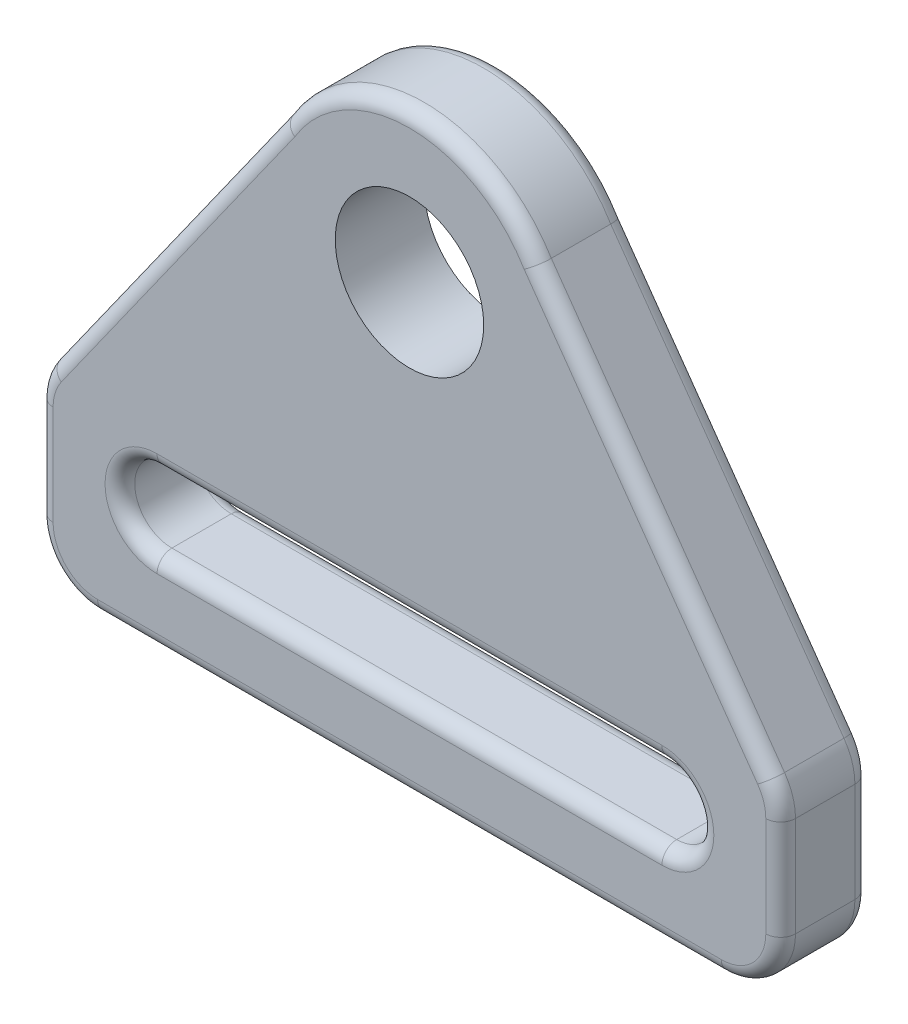
SolidWorks part; units mm, degrees
ref_plane "Front Plane" through (0, 0, 0) normal (0, 0, 1) x (1, 0, 0)
ref_plane "Top Plane" through (0, 0, 0) normal (0, 1, 0) x (1, 0, 0)
ref_plane "Right Plane" through (0, 0, 0) normal (1, 0, 0) x (0, 0, -1)
sketch "Sketch1" plane through (0, 0, 0) normal (0, 0, 1) x (1, 0, 0)
  line L1 (-12.5, 10) -> (12.5, 10)
  line L2 (-12.5, 10) -> (-12.5, -10)
  line L3 (-12.5, -10) -> (12.5, -10)
  line L4 (12.5, 10) -> (12.5, -10)
  line L5 (-12.5, 10) -> (12.5, -10) construction
  line L6 (-12.5, -10) -> (12.5, 10) construction
  point P0 (0, 0)
  dimension "D1" = 25
  dimension "D2" = 20
extrude "Boss-Extrude1" add sketch "Sketch1" along normal blind 3
sketch "Sketch2" plane through (0, 0, 3) normal (0, 0, 1) x (1, 0, 0)
  circle A0 centre (0, 5) radius 2.5
  dimension "D1" = 5
  dimension "D2" = 5
extrude "Cut-Extrude1" cut sketch "Sketch2" against normal blind 3
fillet "Fillet1" radius 2 2 edges at (12.5, -10, 1.5) (-12.5, -10, 1.5)
sketch "Sketch3" plane through (0, 0, 3) normal (0, 0, 1) x (1, 0, 0)
  line L0 (12.5, 10) -> (-12.5, 10) construction
  line L1 (-12.5, -4) -> (-4.2779, 7.5883)
  line L2 (-12.5, 10) -> (-12.5, -8) construction
  line L3 (4.2779, 7.5883) -> (12.5, -4)
  line L4 (12.5, -8) -> (12.5, 10) construction
  line L5 (-10.5, -10) -> (10.5, -10) construction
  line L6 (-12.5, -4) -> (-12.5, 10)
  line L7 (-12.5, 10) -> (0, 10)
  line L8 (12.5, -4) -> (12.5, 10)
  line L9 (12.5, 10) -> (0, 10)
  circle A0 centre (0, 5) radius 5
  line M4 (12.5, -8) -> (12.5, 10)
  line M5 (12.5, 10) -> (-12.5, 10)
  line M6 (-12.5, 10) -> (-12.5, -8)
  dimension "D1" = 6
  dimension "D2" = 6
extrude "Cut-Extrude2" cut sketch "Sketch3" against normal blind 3 contours A0 L1 M5 M6 | A0 L3 M4 M5 region at (-9.0957, 5.3911, 3) region at (9.0957, 5.3911, 3)
sketch "Sketch4" plane through (0, 0, 3) normal (0, 0, 1) x (1, 0, 0)
  line L0 (-8.5, -6) -> (8.5, -6) construction
  line L1 (-8.5, -4.75) -> (8.5, -4.75)
  line L2 (-8.5, -7.25) -> (8.5, -7.25)
  line L3 (-10.5, -10) -> (10.5, -10) construction
  arc A0 (-8.5, -4.75) -> (-8.5, -7.25) centre (-8.5, -6) ccw
  arc A1 (8.5, -7.25) -> (8.5, -4.75) centre (8.5, -6) ccw
  point P2 (0, -6)
  dimension "D1" = 2.5
  dimension "D2" = 0
  dimension "D3" = 17
  dimension "D4" = 4
extrude "Cut-Extrude3" cut sketch "Sketch4" against normal blind 3
fillet "Fillet2" radius 2 2 edges at (12.5, -4, 1.5) (-12.5, -4, 1.5)
fillet "Fillet3" radius 0.5 14 edges at (8.2045, 2.0541, 3) (12.4056, -4.0301, 3) (12.5, -6.3187, 3) (11.9142, -9.4142, 3) (0, -10, 3) (-11.9142, -9.4142, 3) (-12.5, -6.3187, 3) (-12.4056, -4.0301, 3) (-9.75, -6, 3) (0, -4.75, 3) (9.75, -6, 3) (0, 10, 3) (-8.2045, 2.0541, 3) (0, -7.25, 3)
fillet "Fillet4" radius 0.5 14 edges at (-8.2045, 2.0541, 0) (-12.4056, -4.0301, 0) (-12.5, -6.3187, 0) (-11.9142, -9.4142, 0) (0, -10, 0) (11.9142, -9.4142, 0) (12.5, -6.3187, 0) (12.4056, -4.0301, 0) (-9.75, -6, 0) (0, -4.75, 0) (9.75, -6, 0) (0, 10, 0) (8.2045, 2.0541, 0) (0, -7.25, 0)
